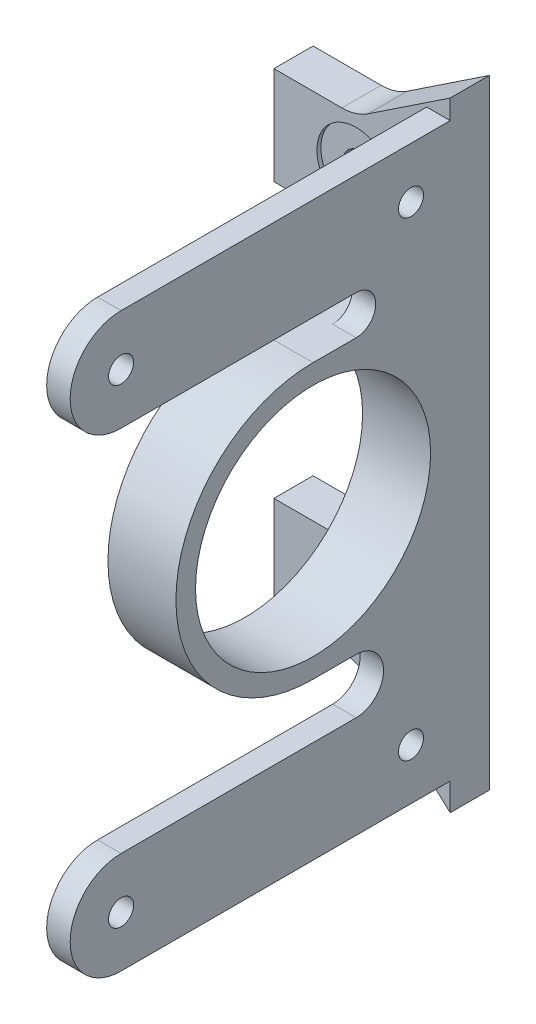
SolidWorks part; units mm, degrees
ref_plane "前视基准面" through (0, 0, 0) normal (0, 0, 1) x (1, 0, 0)
ref_plane "上视基准面" through (0, 0, 0) normal (0, 1, 0) x (1, 0, 0)
ref_plane "右视基准面" through (0, 0, 0) normal (1, 0, 0) x (0, 0, -1)
sketch "草图2" plane through (0, 0, 0) normal (0, 0, 1) x (1, 0, 0)
  line L0 (-14.7736, 24.3382) -> (-14.7736, -35.6618)
  line L1 (-14.7736, -35.6618) -> (30.2264, -35.6618)
  line L2 (7.7264, -35.6618) -> (7.7264, -23.1618)
  line L3 (21.55, -23.1618) -> (-6.0971, -23.1618)
  line L4 (-6.0971, -23.1618) -> (-6.0971, 11.8382)
  line L5 (-6.0971, 11.8382) -> (21.55, 11.8382)
  line L6 (7.7264, 11.8382) -> (7.7264, 24.3382)
  line L7 (30.2264, 24.3382) -> (-14.7736, 24.3382)
  line L8 (7.7264, 28.8603) -> (7.7264, -39.8897) construction
  line L9 (21.55, -23.1618) -> (21.55, 11.8382)
  line L10 (30.2264, 24.3382) -> (30.2264, -35.6618)
  line L11 (-18.1559, -5.6618) -> (33.2411, -5.6618) construction
  point P16 (-6.0971, -5.6618)
  point P17 (-14.7736, -5.6618)
  dimension "D1" = 45
  dimension "D2" = 35
  dimension "D3" = 60
extrude "凸台-拉伸2" add sketch "草图2" along normal blind 5 contours L6 L7 L0 L1 L2 L3 L4 L5 | L10 L7 L6 L5 L9 L3 L2 L1 region at (-3.5236, 23.6974, 0) region at (18.9764, 23.6974, 0)
sketch "草图4" plane through (0, 0, 5) normal (0, 0, 1) x (1, 0, 0)
  line L0 (-18.165, -5.6618) -> (33.9165, -5.6618) construction
  line L1 (-14.7736, 24.3382) -> (-14.7736, -35.6618) construction
  line L2 (-14.7736, -23.1618) -> (-6.0971, -23.1618)
  line L3 (-14.7736, -23.1618) -> (-14.7736, 11.8382)
  line L4 (-14.7736, 11.8382) -> (-6.0971, 11.8382)
  line L5 (-6.0971, -23.1618) -> (-6.0971, 11.8382)
  line L6 (-6.0971, -23.1618) -> (-6.0971, 11.8382) construction
  line L7 (7.7264, -39.813) -> (7.7264, 28.1228) construction
  line L8 (30.2264, 11.8382) -> (21.55, 11.8382)
  line L9 (21.55, -23.1618) -> (21.55, 11.8382)
  line L10 (30.2264, -23.1618) -> (21.55, -23.1618)
  line L11 (30.2264, -23.1618) -> (30.2264, 11.8382)
  point P17 (-14.7736, -5.6618)
  dimension "D1" = 35
extrude "凸台-拉伸15" add sketch "草图4" along normal blind 35
sketch "草图5" plane through (-14.7736, 0, 0) normal (-1, 0, 0) x (0, 0, 1)
  line L0 (0, -5.6618) -> (40, -5.6618)
  line L1 (0, 24.3382) -> (0, -35.6618) construction
  line L2 (40, 11.8382) -> (40, -23.1618) construction
  line L3 (22.5, 11.8382) -> (40, 11.8382)
  line L4 (40, 11.8382) -> (40, -23.1618)
  line L5 (40, -23.1618) -> (22.5, -23.1618)
  circle A0 centre (22.5, -5.6618) radius 17.5
  line M5 (5, -23.1618) -> (40, -23.1618)
  line M6 (40, -23.1618) -> (40, 11.8382)
  line M7 (40, 11.8382) -> (5, 11.8382)
  dimension "D1" = 35
extrude "切除-拉伸1" cut sketch "草图5" against normal blind 45 contours A0 M5 M6 | A0 M6 M7 region at (-14.7736, 7.9293, 36.0911) region at (-14.7736, -19.2528, 36.0911)
sketch "草图6" plane through (-14.7736, 0, 0) normal (-1, 0, 0) x (0, 0, 1)
  circle A0 centre (22.5, -5.6618) radius 15
extrude "切除-拉伸2" cut sketch "草图6" against normal blind 45
fillet "圆角1" radius 5 4 edges at (-6.0971, 11.8382, 2.5) (21.55, 11.8382, 2.5) (-6.0971, -23.1618, 2.5) (21.55, -23.1618, 2.5)
sketch "草图7" plane through (-6.0971, 0, 0) normal (1, 0, 0) x (0, 0, -1)
  circle A0 centre (-22.5, -5.6618) radius 15
  circle A1 centre (-22.5, -5.6618) radius 13
extrude "凸台-拉伸16" add sketch "草图7" against normal blind 1
sketch "草图8" plane through (21.55, 0, 0) normal (-1, 0, 0) x (0, 0, 1)
  circle A0 centre (22.5, -5.6618) radius 15
  circle A1 centre (22.5, -5.6618) radius 10
sketch "草图9" plane through (0, 0, 5) normal (0, 0, 1) x (1, 0, 0)
  line L0 (7.7264, 24.3382) -> (7.7264, -35.6618)
  line L13 (30.2264, 24.3382) -> (-14.7736, 24.3382) construction
  line L14 (-14.7736, -35.6618) -> (30.2264, -35.6618) construction
sketch "草图11" plane through (0, 0, 5) normal (0, 0, 1) x (1, 0, 0)
  line L0 (-14.7736, 18.0882) -> (30.2264, 18.0882)
  line L1 (-14.7736, 24.3382) -> (-14.7736, 11.8382) construction
  line L2 (30.2264, 24.3382) -> (30.2264, 11.8382) construction
  line L3 (7.7264, 24.3382) -> (7.7264, -35.6618) construction
  line L4 (30.2264, 24.3382) -> (-14.7736, 24.3382) construction
  line L5 (-14.7736, -35.6618) -> (30.2264, -35.6618) construction
  line L6 (7.7264, -5.6618) -> (45.6912, -5.6618) construction
  line L7 (45.6912, -5.6618) -> (45.6912, 4.9969) construction
  line L10 (-14.7736, -29.4118) -> (30.2264, -29.4118)
  line L11 (-14.7736, -23.1618) -> (-14.7736, -35.6618) construction
  point P4 (-2.7736, 18.0882)
  point P16 (-2.7736, -29.4118)
  point P18 (18.2264, -29.4118)
  point P25 (18.2264, 18.0882)
  dimension "D1" = 12
split "分割1" trim tools "草图9" bodies to split 111 resulting bodies 117 118
delete or keep bodies "实体-删除/保留 2" type delete bodies bodies 117
sketch "草图17" plane through (0, 0, 5) normal (0, 0, 1) x (1, 0, 0)
  line L0 (21.55, -23.1618) -> (30.2264, -23.1618) construction
  line L1 (30.2264, -43.1618) -> (27.2264, -43.1618)
  line L2 (30.2264, -43.1618) -> (30.2264, -30.1618)
  line L3 (30.2264, -30.1618) -> (27.2264, -30.1618)
  line L4 (27.2264, -43.1618) -> (27.2264, -30.1618)
  line L5 (30.2264, 29.8382) -> (27.2264, 29.8382)
  line L6 (30.2264, 29.8382) -> (30.2264, 16.8382)
  line L7 (30.2264, 16.8382) -> (27.2264, 16.8382)
  line L8 (27.2264, 29.8382) -> (27.2264, 16.8382)
  line L9 (30.2264, 24.3382) -> (30.2264, 11.8382) construction
  line L10 (30.2264, 11.8382) -> (21.55, 11.8382) construction
  point P4 (0, 0)
  dimension "D1" = 3
  dimension "D2" = 3
  dimension "D3" = 13
  dimension "D4" = 13
  dimension "D5" = 7
  dimension "D6" = 5
extrude "凸台-拉伸20" add sketch "草图17" along normal blind 42
sketch "草图18" plane through (30.2264, 0, 0) normal (1, 0, 0) x (0, 0, -1)
  line L1 (-47, -43.1618) -> (-47, -30.1618) construction
  line L2 (-47, -30.1618) -> (-47, -43.1618)
  line L3 (-47, 16.8382) -> (-47, 29.8382)
  arc A0 (-47, 29.8382) -> (-47, 16.8382) centre (-47, 23.3382) ccw
  arc A1 (-47, -30.1618) -> (-47, -43.1618) centre (-47, -36.6618) ccw
  point P1 (-47, 24.3382)
  point P2 (-47, 24.3382)
  point P3 (-47, 24.3382)
  point P6 (0, 0)
  point P12 (0, 0)
  point P16 (-47, 24.3382)
  point P17 (-47, 24.3382)
  point P18 (0, 0)
  point P19 (-47, 24.3382)
  point P20 (0, 0)
  point P21 (0, 0)
  point P22 (-47, 26.4684)
  point P23 (-47, 29.8382)
extrude "凸台-拉伸21" add sketch "草图18" against normal blind 3
sketch "草图19" plane through (30.2264, 0, 0) normal (1, 0, 0) x (0, 0, -1)
  circle A0 centre (-47, 23.3382) radius 1.6
  circle A1 centre (-47, -36.6618) radius 1.6
  circle A2 centre (-10, 23.3382) radius 1.6
  circle A3 centre (-10, -36.6618) radius 1.6
  dimension "D1" = 37
  dimension "D2" = 37
extrude "切除-拉伸3" cut sketch "草图19" against normal blind 3
sketch "草图21" plane through (0, 0, 5) normal (0, 0, 1) x (1, 0, 0)
  line L0 (18.2264, -35.6618) -> (30.2264, -35.6618)
  line L1 (7.7264, -35.6618) -> (27.2264, -35.6618) construction
  line L2 (30.2264, -43.1618) -> (30.2264, -30.1618) construction
  line L3 (30.2264, -35.6618) -> (30.2264, -46.6618)
  line L4 (30.2264, -46.6618) -> (18.2264, -35.6618)
  line L5 (18.2264, 24.3382) -> (30.2264, 24.3382)
  line L6 (27.2264, 24.3382) -> (7.7264, 24.3382) construction
  line L7 (30.2264, 16.8382) -> (30.2264, 29.8382) construction
  line L8 (30.2264, 24.3382) -> (30.2264, 32.3382)
  line L9 (30.2264, 32.3382) -> (18.2264, 24.3382)
  dimension "D1" = 11
  dimension "D2" = 12
  dimension "D3" = 12
  dimension "D4" = 8
extrude "凸台-拉伸22" add sketch "草图21" against normal blind 5
sketch "草图24" plane through (30.2264, 0, 0) normal (1, 0, 0) x (0, 0, -1)
  line L0 (-47, -30.1618) -> (-5, -30.1618) construction
  line L1 (-17, -23.1618) -> (-5, -23.1618)
  line L2 (-5, -23.1618) -> (-5, -30.1618)
  line L3 (-5, 24.3382) -> (-5, -35.6618) construction
  line L4 (-5, -30.1618) -> (-17, -30.1618)
  line L5 (-22.5, 11.8382) -> (-5, 11.8382) construction
  line L6 (-47, 16.8382) -> (-5, 16.8382) construction
  line L7 (-17, 11.8382) -> (-5, 11.8382)
  line L8 (-5, 11.8382) -> (-5, 16.8382)
  line L9 (-5, 16.8382) -> (-17, 16.8382)
  arc A0 (-17, -30.1618) -> (-17, -23.1618) centre (-17, -26.6618) ccw
  arc A1 (-17, 11.8382) -> (-17, 16.8382) centre (-17, 14.3382) ccw
  point P2 (0, 0)
extrude "凸台-拉伸25" add sketch "草图24" against normal blind 3
hole_wizard "打孔尺寸(%根据六角头螺)栓 全螺纹的类型1" positions "3D草图2" profile "草图31" counterbore size "M4" standard "GB"
sketch3d "3D草图2"
  point P0 (18.2264, 18.0882, 5)
  point P3 (18.2264, -29.4118, 5)
sketch "草图31" plane through (18.2264, 18.0882, 5) normal (1, 0, 0) x (0, -1, 0)
  line L0 (0, 0) -> (0, 6.2919)
  line L1 (0, 6.2919) -> (2.15, 5)
  line L2 (2.15, 5) -> (2.15, 0.5)
  line L3 (2.15, 0.5) -> (5, 0.5)
  line L4 (5, 0.5) -> (5, 0)
  line L5 (5, 0) -> (0, 0)
  line L10 (0, 6.2919) -> (-2.15, 5) construction
  line L11 (0, -6.35) -> (0, 107.95) construction
  dimension "孔直径" = 4.3
  dimension "孔深度" = 5
  dimension "柱形沉头孔直径" = 10
  dimension "柱形沉头孔深度" = 0.5
  dimension "导头角度" = 118
fillet "圆角2" radius 6 2 edges at (18.2264, -35.6618, 2.5) (18.2264, 24.3382, 2.5)
